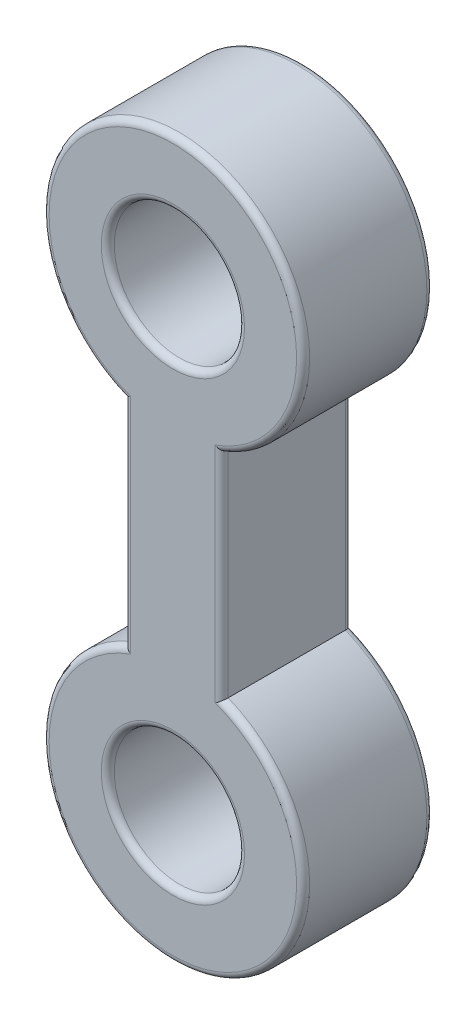
SolidWorks part; units mm, degrees
ref_plane "Front Plane" through (0, 0, 0) normal (0, 0, 1) x (1, 0, 0)
ref_plane "Top Plane" through (0, 0, 0) normal (0, 1, 0) x (1, 0, 0)
ref_plane "Right Plane" through (0, 0, 0) normal (1, 0, 0) x (0, 0, -1)
sketch "Sketch1" plane through (0, 0, 0) normal (0, 0, 1) x (1, 0, 0)
  line L0 (0, 0) -> (0, -1778) construction
  line L1 (190.5, -470.9286) -> (190.5, -1307.0714)
  line L3 (-190.5, -470.9286) -> (-190.5, -1307.0714)
  arc A4 (190.5, -470.9286) -> (-190.5, -470.9286) centre (0, 0) ccw
  circle A5 centre (0, 0) radius 254
  arc A6 (190.5, -1307.0714) -> (-190.5, -1307.0714) centre (0, -1778) cw
  circle A7 centre (0, -1778) radius 254
  dimension "D1" = 1016
  dimension "D2" = 508
  dimension "D3" = 1778
  dimension "D4" = 190.5
extrude "Boss-Extrude1" add sketch "Sketch1" along normal mid plane 508
fillet "Fillet1" radius 25.4 12 edges at (-254, -1778, 254) (190.5, -889, 254) (0, -2286, 254) (-190.5, -889, 254) (0, 508, 254) (254, 0, 254) (-254, -1778, -254) (254, 0, -254) (-190.5, -889, -254) (0, -2286, -254) (190.5, -889, -254) (0, 508, -254)
